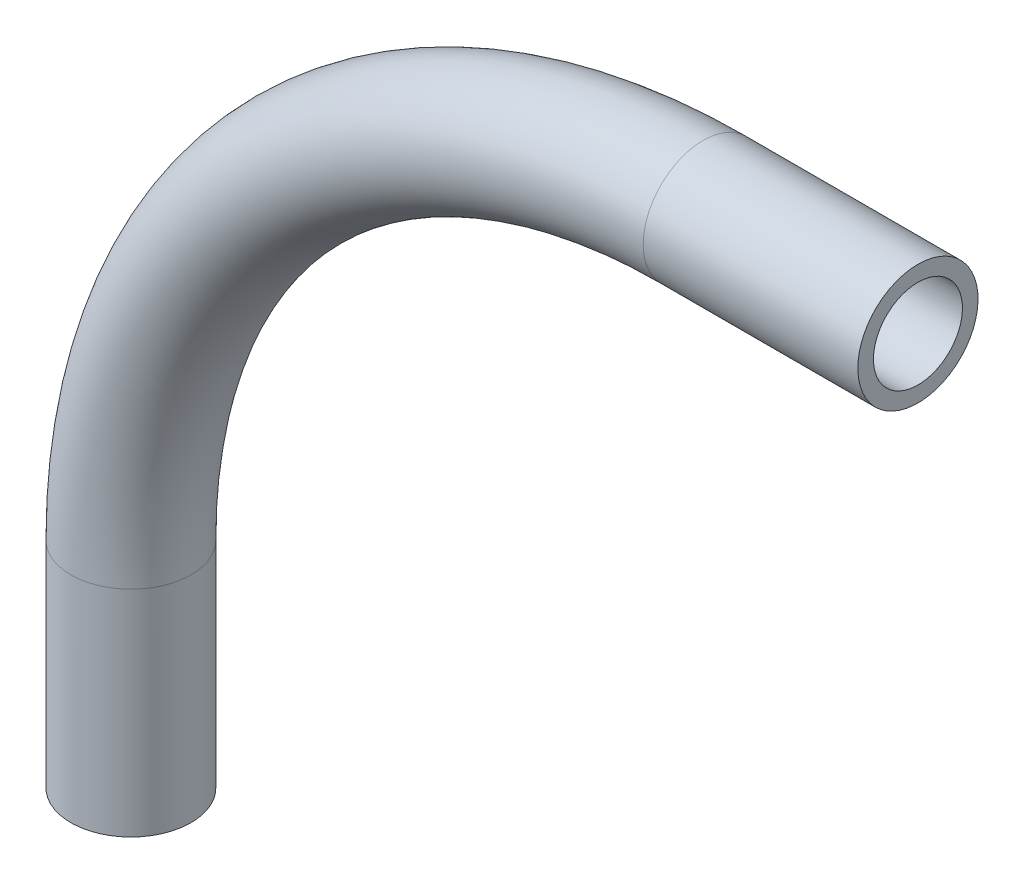
SolidWorks part; units mm, degrees
material "PVC Rigid"
ref_plane "front" through (0, 0, 0) normal (0, 0, 1) x (1, 0, 0)
ref_plane "top" through (0, 0, 0) normal (0, 1, 0) x (1, 0, 0)
ref_plane "side" through (0, 0, 0) normal (1, 0, 0) x (0, 0, -1)
sketch "ElbowArc" plane through (0, 0, 0) normal (0, 0, 1) x (1, 0, 0)
  arc A0 (-101.6, 0) -> (0, 101.6) centre (0, 0) cw
  dimension "BendAngle" = 90
  dimension "BendRadius" = 101.6
sketch "Route" plane through (0, 0, 0) normal (0, 1, 0) x (1, 0, 0)
  circle A0 centre (-101.6, 0) radius 10.668
  dimension "ElbowOD" = 21.336
  dimension "BendRadius" = 101.6
sweep "Elbow" add profiles "Route" path "ElbowArc"
shell "ElbowShell" thickness 2.7686 removed face at (0, 101.6, 10.668) removed face at (-101.6, 0, 10.668)
sketch3d "3DSketch1"
  circle A0 centre (0, 101.6, 0) radius 7.8994 construction
  circle A1 centre (-101.6, 0, 0) radius 10.668 construction
  circle A2 centre (0, 101.6, 0) radius 7.8994 construction
  point P4 (-101.6, 0, 0)
  point P7 (-101.6, 10.668, 0)
  point P14 (7.8994, 101.6, 0)
  point P16 (7.8994, 101.6, 0)
ref_plane "Plane1" through (0, 0, 0) normal (1, 0, 0) x (0, 0, -1)
ref_plane "Plane2" through (0, 0, 0) normal (0, -1, 0) x (1, 0, 0)
sketch "Sketch2" plane through (0, 0, 0) normal (1, 0, 0) x (0, 0, -1)
  circle A0 centre (0, 101.6) radius 10.668 construction
  circle A1 centre (0, 101.6) radius 7.8994 construction
  circle A2 centre (0, 101.6) radius 10.668
  circle A3 centre (0, 101.6) radius 7.8994
extrude "ElbowExtension-Extrude1" add sketch "Sketch2" along normal blind 38.1
sketch "Sketch3" plane through (0, 0, 0) normal (0, -1, 0) x (1, 0, 0)
  circle A0 centre (-101.6, 0) radius 7.8994 construction
  circle A1 centre (-101.6, 0) radius 10.668 construction
  circle A2 centre (-101.6, 0) radius 7.8994
  circle A3 centre (-101.6, 0) radius 10.668
extrude "ElbowExtension-Extrude2" add sketch "Sketch3" along normal blind 38.1
sketch "Sketch4" plane through (0, 0, 0) normal (1, 0, 0) x (0, 0, -1)
  point P0 (0, 101.6)
sketch "Sketch5" plane through (0, 0, 0) normal (0, -1, 0) x (1, 0, 0)
  point P0 (-101.6, 0)
other "CPoint1" parameters "Diameter"=12.7, "StubLength"=0
ref_axis "Axis1" through (10, 101.6, 0) along (-1, 0, 0)
other "CPoint2" parameters "Diameter"=12.7, "StubLength"=0
ref_axis "Axis2" through (-101.6, -10, 0) along (0, 1, 0)
other "RPoint1"
